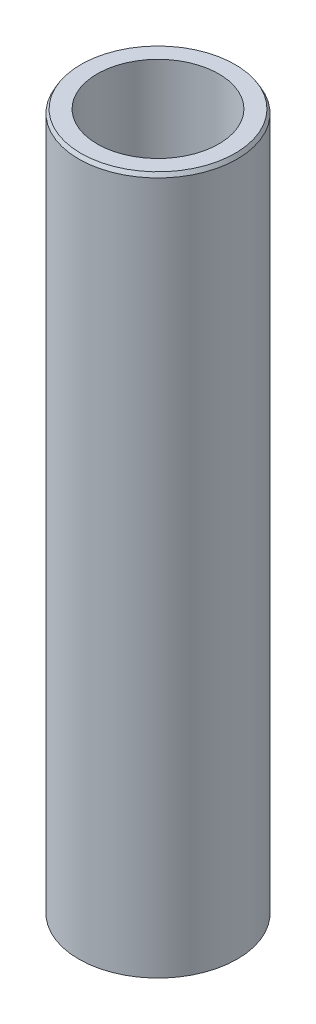
SolidWorks part; units mm, degrees
ref_plane "Front Plane" through (0, 0, 0) normal (0, 0, 1) x (1, 0, 0)
ref_plane "Top Plane" through (0, 0, 0) normal (0, 1, 0) x (1, 0, 0)
ref_plane "Right Plane" through (0, 0, 0) normal (1, 0, 0) x (0, 0, -1)
sketch "Sketch1" plane through (0, 0, 0) normal (0, 1, 0) x (1, 0, 0)
  circle A0 centre (0, 0) radius 55
  dimension "SHAFT_OD" = 110
extrude "Boss-Extrude1" add sketch "Sketch1" along normal blind 485.0558
sketch "Sketch2" plane through (0, 0, 0) normal (0, 1, 0) x (1, 0, 0)
  circle A0 centre (0, 0) radius 42.1822
  dimension "BORE_D" = 84.3644
extrude "Cut-Extrude1" cut sketch "Sketch2" along normal through all
chamfer "Chamfer1" distance 2.629 angle 30 2 edges at (0, 485.0558, 55) (0, 0, 55) first distance on face at (0, 485.0558, 55) first distance on face at (0, 0, 42.1822)
